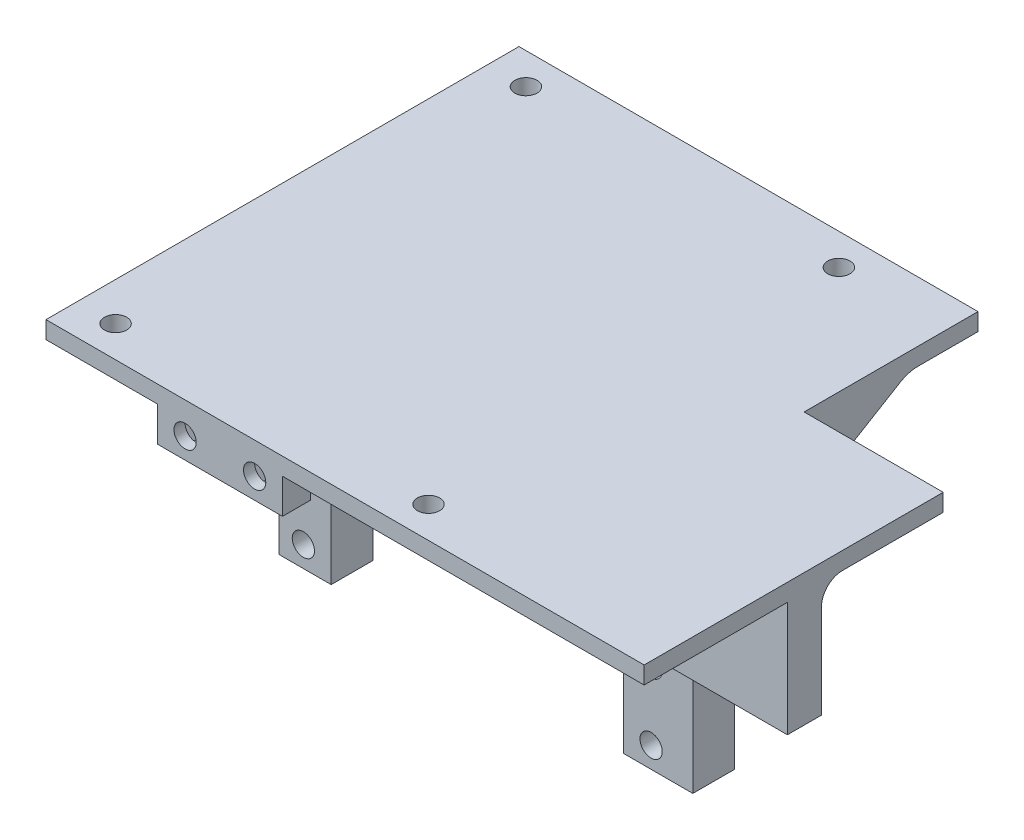
SolidWorks part; units mm, degrees
ref_plane "前视基准面" through (0, 0, 0) normal (0, 0, 1) x (1, 0, 0)
ref_plane "上视基准面" through (0, 0, 0) normal (0, 1, 0) x (1, 0, 0)
ref_plane "右视基准面" through (0, 0, 0) normal (1, 0, 0) x (0, 0, -1)
other "Configuration Table"
sketch "Orthogonal chassis plate primary profile" plane through (0, 0, 0) normal (0, 0, 1) x (1, 0, 0)
  line L0 (-25, 29) -> (41, 29)
  line L1 (41, 29) -> (41, 33)
  line L2 (41, 33) -> (-25, 33)
  line L3 (-25, 33) -> (-25, 29)
extrude "Orthogonal chassis plate primary" add sketch "Orthogonal chassis plate primary profile" along normal blind 25.1 from offset 15 offset against normal yes
sketch "Orthogonal chassis plate guide side profile" plane through (0, 0, 0) normal (0, 0, 1) x (1, 0, 0)
  line L0 (-25, 29) -> (84, 29)
  line L1 (84, 29) -> (84, 33)
  line L2 (84, 33) -> (-25, 33)
  line L3 (-25, 33) -> (-25, 29)
extrude "Orthogonal chassis plate guide side" add sketch "Orthogonal chassis plate guide side profile" along normal blind 43 from offset 10
sketch "Horizontal servo seat uprights profile" plane through (0, 0, 0) normal (0, 0, 1) x (1, 0, 0)
  line L0 (-18.5, -8) -> (-11, -8)
  line L1 (-11, -8) -> (-11, 29.1)
  line L2 (-11, 29.1) -> (-18.5, 29.1)
  line L4 (31, -8) -> (41, -8)
  line L5 (41, -8) -> (41, 29.1)
  line L6 (41, 29.1) -> (31, 29.1)
  line L7 (31, 29.1) -> (31, -8)
  line L12 (-18.5, 29.1) -> (-18.5, -8)
extrude "Horizontal servo seat uprights" add sketch "Horizontal servo seat uprights profile" along normal blind 6 from offset 20
sketch "Side mounting face for MGN7 rail profile" plane through (0, 0, 0) normal (0, 0, 1) x (1, 0, 0)
  line L0 (-17, 12.5) -> (83, 12.5)
  line L1 (83, 12.5) -> (83, 29.1)
  line L2 (83, 29.1) -> (-17, 29.1)
  line L3 (-17, 29.1) -> (-17, 12.5)
extrude "Side mounting face for MGN7 rail" add sketch "Side mounting face for MGN7 rail profile" along normal blind 4.9 from offset 27.5
sketch "Horizontal limit bracket foot support profile" plane through (0, 0, 0) normal (0, 0, 1) x (1, 0, 0)
  line L0 (-9, 24) -> (9, 24)
  line L1 (9, 24) -> (9, 29.1)
  line L2 (9, 29.1) -> (-9, 29.1)
  line L3 (-9, 29.1) -> (-9, 24)
extrude "Horizontal limit bracket foot support" add sketch "Horizontal limit bracket foot support profile" along normal blind 4 from offset 49
sketch "Chassis mounting hole layout 45 x 41 mm profile" plane through (0, 0, 0) normal (0, 1, 0) x (1, 0, 0)
  circle A0 centre (-19.5, 10.5) radius 1.6
  circle A1 centre (-19.5, -48.5) radius 1.6
  circle A2 centre (25.5, 10.5) radius 1.6
  circle A3 centre (25.5, -48.5) radius 1.6
  circle A4 centre (70.5, -48.5) radius 1.6
  point P12 (-24.5, 14.5)
  dimension "D3" = 3.2
  dimension "D6" = 2
  dimension "D9" = 3.2
  dimension "D5" = 59
  dimension "D1" = 5
  dimension "D2" = 4
  dimension "D4" = 2
  dimension "D7" = 50
  dimension "D8" = 4
extrude "Chassis mounting hole layout 45 x 41 mm" cut sketch "Chassis mounting hole layout 45 x 41 mm profile" along normal blind 4.2 from offset 28.9
sketch "Servo mount 50 x 10 mm pitch profile" plane through (0, 0, 0) normal (0, 0, 1) x (1, 0, 0)
  circle A0 centre (-15, -5) radius 1.6
  circle A1 centre (-15, 5) radius 1.6
  circle A2 centre (35, -5) radius 1.6
  circle A3 centre (35, 5) radius 1.6
  point P8 (-21, -8)
  dimension "D3" = 3.2
  dimension "D6" = 3.2
  dimension "D9" = 3.2
  dimension "D12" = 3.2
  dimension "D1" = 6
  dimension "D2" = 3
  dimension "D4" = 6
  dimension "D5" = 13
  dimension "D7" = 56
  dimension "D8" = 3
  dimension "D10" = 56
  dimension "D11" = 13
extrude "Servo mount 50 x 10 mm pitch" cut sketch "Servo mount 50 x 10 mm pitch profile" along normal blind 6.2 from offset 19.9
sketch "Guide M2 mounting pilots 15 mm pitch profile" plane through (0, 0, 0) normal (0, 0, 1) x (1, 0, 0)
  circle A0 centre (-12, 19) radius 1.05
  circle A1 centre (3, 19) radius 1.05
  circle A2 centre (18, 19) radius 1.05
  circle A3 centre (33, 19) radius 1.05
  circle A4 centre (48, 19) radius 1.05
  circle A5 centre (63, 19) radius 1.05
  circle A6 centre (78, 19) radius 1.05
  point P14 (-17, 12)
  dimension "D3" = 2.1
  dimension "D6" = 2.1
  dimension "D9" = 2.1
  dimension "D12" = 2.1
  dimension "D15" = 2.1
  dimension "D18" = 2.1
  dimension "D21" = 2.1
  dimension "D1" = 5
  dimension "D2" = 7
  dimension "D4" = 20
  dimension "D5" = 7
  dimension "D7" = 35
  dimension "D8" = 7
  dimension "D10" = 50
  dimension "D11" = 7
  dimension "D13" = 65
  dimension "D14" = 7
  dimension "D16" = 80
  dimension "D17" = 7
  dimension "D19" = 95
  dimension "D20" = 7
extrude "Guide M2 mounting pilots 15 mm pitch" cut sketch "Guide M2 mounting pilots 15 mm pitch profile" along normal blind 5.05 from offset 27.45
sketch "Stop mounting two M3 pilots 10 mm pitch profile" plane through (0, 0, 0) normal (0, 0, 1) x (1, 0, 0)
  circle A0 centre (-5, 27) radius 1.6
  circle A1 centre (5, 27) radius 1.6
  point P4 (-9, 24)
  dimension "D3" = 3.2
  dimension "D6" = 3.2
  dimension "D1" = 4
  dimension "D2" = 3
  dimension "D4" = 14
  dimension "D5" = 3
extrude "Stop mounting two M3 pilots 10 mm pitch" cut sketch "Stop mounting two M3 pilots 10 mm pitch profile" along normal blind 4.2 from offset 48.9
fillet "圆角2" radius 3 1 edges at (33, 29, 27.5)
sketch "草图3" plane through (0, 29, 0) normal (0, -1, 0) x (-1, 0, 0)
  line L0 (9, -49) -> (-9, -49) construction
  line L1 (9, -49) -> (-9, -49)
  line L2 (9, -49) -> (9, -46)
  line L3 (9, -46) -> (-9, -46)
  line L4 (-9, -49) -> (-9, -46)
  line L5 (9, -53) -> (9, -49) construction
  dimension "D1" = 18
  dimension "D2" = 3
extrude "切除-拉伸1" cut sketch "草图3" against normal blind 2
sketch "草图4" plane through (0, 0, 49) normal (0, 0, -1) x (-1, 0, 0)
  line L0 (9, 24) -> (-9, 24) construction
  line L1 (-3.2679, 30) -> (-6.7321, 30)
  line L2 (-6.7321, 30) -> (-8.4641, 27)
  line L3 (-8.4641, 27) -> (-6.7321, 24)
  line L4 (-6.7321, 24) -> (-3.2679, 24)
  line L5 (-3.2679, 24) -> (-1.5359, 27)
  line L6 (-1.5359, 27) -> (-3.2679, 30)
  line L7 (6.7321, 30) -> (3.2679, 30)
  line L8 (3.2679, 30) -> (1.5359, 27)
  line L9 (1.5359, 27) -> (3.2679, 24)
  line L10 (3.2679, 24) -> (6.7321, 24)
  line L11 (6.7321, 24) -> (8.4641, 27)
  line L12 (8.4641, 27) -> (6.7321, 30)
  circle A0 centre (-5, 27) radius 3 construction
  circle A1 centre (5, 27) radius 3 construction
  dimension "D1" = 6
  dimension "D2" = 3
extrude "切除-拉伸2" cut sketch "草图4" against normal blind 2.4
sketch "草图5" plane through (-11, 0, 0) normal (1, 0, 0) x (0, 0, -1)
  line L0 (-20, 29) -> (5, 29)
  line L1 (-10, 29) -> (15, 29) construction
  line L2 (5, 29) -> (-20, 14)
  line L3 (-20, -8) -> (-20, 29) construction
  line L4 (-20, 14) -> (-20, 29)
  dimension "D1" = 25
  dimension "D2" = 15
extrude "凸台-拉伸3" add sketch "草图5" against normal blind 7.5
sketch "草图6" plane through (31, 0, 0) normal (-1, 0, 0) x (0, 0, 1)
  line L0 (20, 29) -> (-5, 29)
  line L1 (-5, 29) -> (20, 14)
  line L2 (20, 29) -> (20, -8) construction
  line L3 (20, 14) -> (20, 29)
  dimension "D1" = 25
  dimension "D2" = 15
extrude "凸台-拉伸4" add sketch "草图6" against normal blind 10
fillet "圆角3" radius 5 4 edges at (36, 29, -5) (-14.75, 29, -5) (-14.75, 14, 20) (36, 14, 20)
sketch "草图7" plane through (0, 0, 53) normal (0, 0, 1) x (1, 0, 0)
  line L0 (84, 29) -> (84, 33) construction
  line L1 (-25, 33) -> (84, 33)
  line L2 (-25, 33) -> (-25, 31.5)
  line L3 (-25, 31.5) -> (84, 31.5)
  line L4 (84, 33) -> (84, 31.5)
  dimension "D1" = 1.5
extrude "切除-拉伸3" cut sketch "草图7" against normal blind 80
sketch "草图8" plane through (0, 31.5, 0) normal (0, 1, 0) x (1, 0, 0)
  line L0 (-25, -53) -> (84, -53) construction
  line L1 (84, -10) -> (61, -10)
  line L2 (84, -10) -> (84, -53)
  line L3 (84, -53) -> (61, -53)
  line L4 (61, -10) -> (61, -53)
  dimension "D1" = 23
extrude "切除-拉伸4" cut sketch "草图8" against normal blind 30
